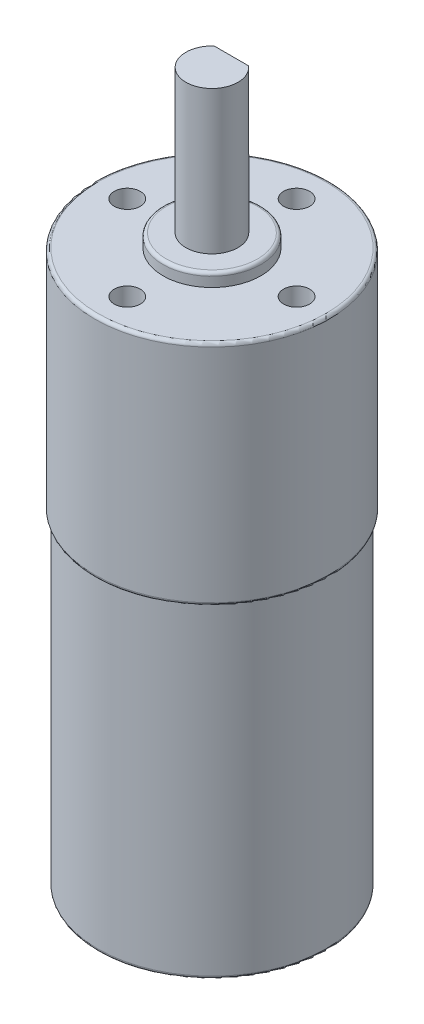
SolidWorks part; units mm, degrees
ref_plane "前视基准面" through (0, 0, 0) normal (0, 0, 1) x (1, 0, 0)
ref_plane "上视基准面" through (0, 0, 0) normal (0, 1, 0) x (1, 0, 0)
ref_plane "右视基准面" through (0, 0, 0) normal (1, 0, 0) x (0, 0, -1)
sketch "草图1" plane through (0, 0, 0) normal (0, 1, 0) x (1, 0, 0)
  circle A0 centre (0, 0) radius 17.5
  dimension "D1" = 35
extrude "凸台-拉伸1" add sketch "草图1" along normal blind 50
sketch "草图2" plane through (0, 50, 0) normal (0, 1, 0) x (1, 0, 0)
  circle A0 centre (0, 0) radius 17.5
sketch "草图3" plane through (0, 50, 0) normal (0, 1, 0) x (1, 0, 0)
  circle A0 centre (0, 0) radius 18
  dimension "D1" = 36
extrude "凸台-拉伸4" add sketch "草图3" along normal blind 35
sketch "草图4" plane through (0, 85, 0) normal (0, 1, 0) x (1, 0, 0)
  circle A0 centre (0, 0) radius 7.5
  dimension "D1" = 15
extrude "凸台-拉伸5" add sketch "草图4" along normal blind 2
sketch "草图5" plane through (0, 87, 0) normal (0, 1, 0) x (1, 0, 0)
  circle A0 centre (0, 0) radius 4
extrude "凸台-拉伸6" add sketch "草图5" along normal blind 22
sketch "草图6" plane through (0, 85, 0) normal (0, 1, 0) x (1, 0, 0)
  circle A0 centre (0, 13) radius 2
  circle A2 centre (13, 0) radius 2
  circle A3 centre (0, -13) radius 2
  circle A4 centre (-13, 0) radius 2
  point P5 (0, 0)
  point P14 (0, 0)
  dimension "D1" = 4
  dimension "D2" = 13
  dimension "D3" = 4
extrude "切除-拉伸1" cut sketch "草图6" against normal blind 5
sketch "草图7" plane through (0, 109, 0) normal (0, 1, 0) x (1, 0, 0)
  line L1 (-4.4458, 4.719) -> (3.6159, 4.719)
  line L2 (-4.4458, 4.719) -> (-4.4458, 3)
  line L3 (-4.4458, 3) -> (3.6159, 3)
  line L4 (3.6159, 4.719) -> (3.6159, 3)
  dimension "D1" = 3
extrude "切除-拉伸2" cut sketch "草图7" against normal blind 18
fillet "圆角10" radius 0.5 1 edges at (0, 85, 18)
fillet "圆角11" radius 0.5 1 edges at (0, 50, 18)
fillet "圆角12" radius 0.5 1 edges at (0, 0, 17.5)
fillet "圆角13" radius 0.5 1 edges at (0, 87, 7.5)
